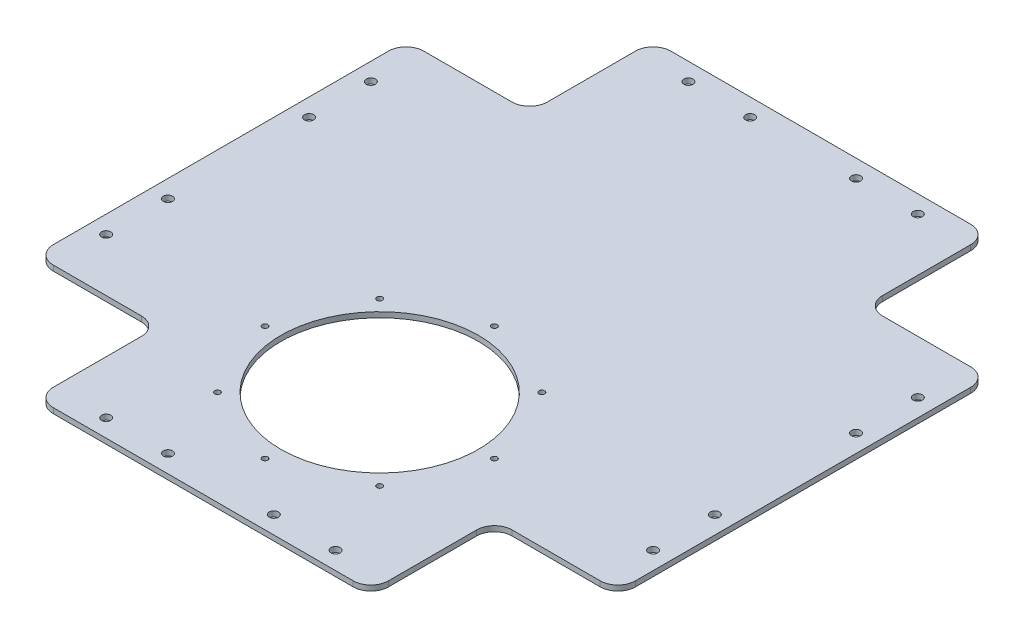
SolidWorks part; units mm, degrees
ref_plane "Front Plane" through (0, 0, 0) normal (0, 0, 1) x (1, 0, 0)
ref_plane "Top Plane" through (0, 0, 0) normal (0, 1, 0) x (1, 0, 0)
ref_plane "Right Plane" through (0, 0, 0) normal (1, 0, 0) x (0, 0, -1)
sketch "Sketch1" plane through (0, 0, 0) normal (0, 1, 0) x (1, 0, 0)
  line L0 (0, 100) -> (330, 100) construction
  line L1 (0, 0) -> (330, 0) construction
  line L2 (0, 0) -> (0, 350) construction
  line L3 (0, 350) -> (330, 350) construction
  line L4 (330, 0) -> (330, 350) construction
  line L5 (0, 0) -> (330, 0)
  line L6 (0, 0) -> (0, 280)
  line L7 (0, 280) -> (330, 280)
  line L8 (330, 0) -> (330, 280)
  line L9 (70, 280) -> (260, 280)
  line L10 (70, 280) -> (70, 350)
  line L11 (70, 350) -> (260, 350)
  line L12 (260, 280) -> (260, 350)
  line L14 (0, 0) -> (70, 0)
  line L15 (0, 0) -> (0, 70)
  line L16 (0, 70) -> (70, 70)
  line L17 (70, 0) -> (70, 70)
  line L18 (330, 0) -> (260, 0)
  line L19 (330, 0) -> (330, 70)
  line L20 (330, 70) -> (260, 70)
  line L21 (260, 0) -> (260, 70)
  circle A0 centre (165, 100) radius 56
  point P11 (165, 350)
  point P12 (165, 350)
  dimension "D5" = 112
  dimension "D1" = 330
  dimension "D2" = 350
  dimension "D3" = 70
  dimension "D4" = 70
  dimension "D6" = 70
  dimension "D7" = 100
extrude "Boss-Extrude1" add sketch "Sketch1" along normal blind 3 contours L5 L8 L7 L6 A0 | L7 L12 L11 L10 region at (165, 0, -159.5618) region at (165, 0, -315)
fillet "Fillet1" radius 10 12 edges at (330, 1.5, -280) (260, 1.5, -350) (260, 1.5, -280) (70, 1.5, -280) (70, 1.5, -350) (0, 1.5, -280) (260, 1.5, 0) (330, 1.5, -70) (260, 1.5, -70) (70, 1.5, 0) (70, 1.5, -70) (0, 1.5, -70)
sketch "Sketch2" plane through (0, 3, 0) normal (0, 1, 0) x (1, 0, 0)
  line L0 (80, 350) -> (250, 350) construction
  line L1 (0, 0) -> (330, 0) construction
  line L2 (0, 0) -> (0, 350) construction
  line L3 (0, 350) -> (330, 350) construction
  line L4 (330, 0) -> (330, 350) construction
  line L5 (330, 80) -> (330, 270) construction
  line L6 (10, 10) -> (10, 340) construction
  line L7 (10, 340) -> (320, 340) construction
  line L8 (320, 10) -> (320, 340) construction
  line L9 (10, 10) -> (320, 10) construction
  line L10 (70, 290) -> (70, 340) construction
  line L11 (260, 290) -> (260, 340) construction
  line L12 (270, 280) -> (320, 280) construction
  line L13 (260, 10) -> (260, 60) construction
  line L14 (70, 10) -> (70, 60) construction
  line L15 (320, 70) -> (270, 70) construction
  line L16 (10, 70) -> (60, 70) construction
  line L17 (10, 280) -> (60, 280) construction
  circle A0 centre (100, 340) radius 2.6
  circle A1 centre (135, 340) radius 2.6
  circle A2 centre (195, 340) radius 2.6
  circle A3 centre (230, 340) radius 2.6
  circle A4 centre (10, 250) radius 2.6
  circle A5 centre (10, 215) radius 2.6
  circle A6 centre (10, 100) radius 2.6
  circle A7 centre (10, 135) radius 2.6
  circle A8 centre (100, 10) radius 2.6
  circle A9 centre (135, 10) radius 2.6
  circle A10 centre (195, 10) radius 2.6
  circle A11 centre (230, 10) radius 2.6
  circle A12 centre (320, 100) radius 2.6
  circle A13 centre (320, 135) radius 2.6
  circle A14 centre (320, 250) radius 2.6
  circle A15 centre (320, 215) radius 2.6
  circle A16 centre (165, 100) radius 65 construction
  circle A18 centre (165, 165) radius 1.6
  circle A19 centre (210.9619, 145.9619) radius 1.6
  circle A20 centre (230, 100) radius 1.6
  circle A21 centre (210.9619, 54.0381) radius 1.6
  circle A22 centre (165, 35) radius 1.6
  circle A23 centre (119.0381, 54.0381) radius 1.6
  circle A24 centre (100, 100) radius 1.6
  circle A25 centre (119.0381, 145.9619) radius 1.6
  point P84 (165, 100)
  dimension "D2" = 5.2
  dimension "D4" = 35
  dimension "D5" = 35
  dimension "D7" = 30
  dimension "D8" = 35
  dimension "D10" = 35
  dimension "D12" = 35
  dimension "D14" = 35
  dimension "D16" = 35
  dimension "D17" = 30
  dimension "D18" = 35
  dimension "D19" = 130
  dimension "D20" = 3.2
  dimension "D3" = 30
  dimension "D6" = 30
  dimension "D9" = 30
  dimension "D11" = 30
  dimension "D13" = 30
  dimension "D15" = 30
  dimension "D1" = 10
  dimension "D21" = 8
extrude "Cut-Extrude1" cut sketch "Sketch2" against normal through all
sketch "Sketch3" plane through (0, 3, 0) normal (0, 1, 0) x (1, 0, 0)
  circle A0 centre (165, 100) radius 56
  circle A1 centre (165, 100) radius 47.5
  circle A2 centre (165, 100) radius 56 construction
  dimension "D1" = 95
extrude "Boss-Extrude2" [suppressed] add sketch "Sketch3" against normal up to surface (3 mm away) up to face at (320, 0, -132.4)
